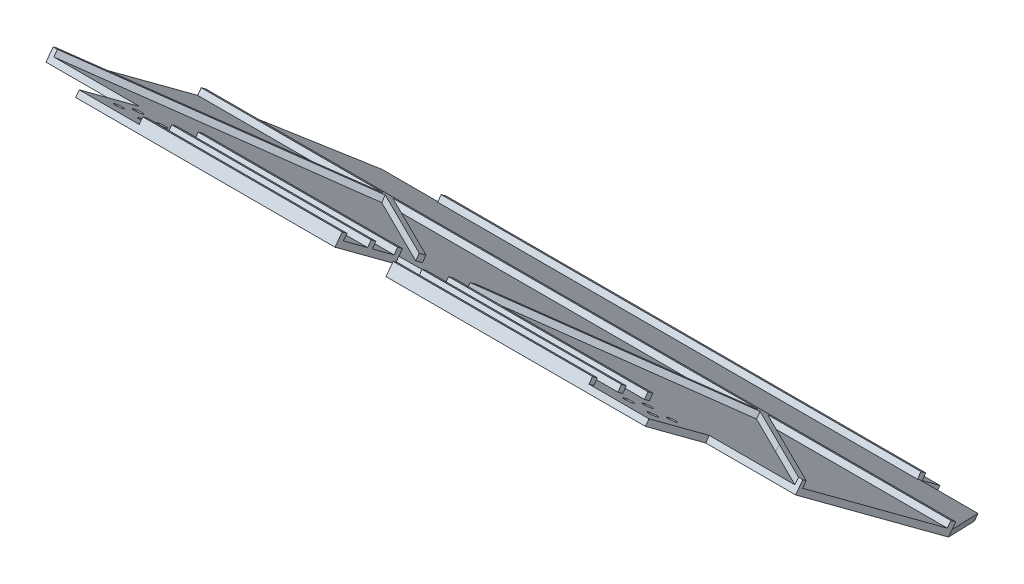
SolidWorks part; units mm, degrees
ref_plane "前视基准面" through (0, 0, 0) normal (0, 0, 1) x (1, 0, 0)
ref_plane "上视基准面" through (0, 0, 0) normal (0, 1, 0) x (1, 0, 0)
ref_plane "右视基准面" through (0, 0, 0) normal (1, 0, 0) x (0, 0, -1)
other "Configuration Table"
sketch "草图1" plane through (0, 0, 0) normal (0, 0, 1) x (1, 0, 0)
  line L11 (-17.5, -167.5) -> (167.5, -167.5)
  line L12 (-17.5, -167.5) -> (-17.5, 17.5)
  line L13 (-17.5, 17.5) -> (167.5, 17.5)
  line L14 (167.5, -167.5) -> (167.5, 17.5)
sketch "草图3" plane through (0, 0, 20) normal (0, 0, 1) x (1, 0, 0)
  line L7 (-32.4602, 32.2748) -> (182.5398, 32.2748)
  line L8 (-32.4602, 32.2748) -> (-32.4602, -182.7252)
  line L9 (-32.4602, -182.7252) -> (182.5398, -182.7252)
  line L10 (182.5398, 32.2748) -> (182.5398, -182.7252)
  point P12 (75.0398, -75.2252)
  dimension "D1" = 215
  dimension "D2" = 215
loft "放样1" add profiles "草图3", "草图1" connector at (-32.4602, 32.2748, 20) connector at (-17.5, 17.5, 0)
shell "抽壳2" thickness 3 removed face at (75.0398, -75.2252, 20)
sketch "草图4" plane through (0, 0, 3) normal (0, 0, 1) x (1, 0, 0)
  line L0 (75, 15.9864) -> (75, -182.7252)
  line L1 (166.0024, 15.9864) -> (-15.9976, 15.9864) construction
  line L2 (-32.4602, -182.7252) -> (182.5398, -182.7252) construction
  line L3 (-32.4602, -75.2252) -> (182.5398, -75.2252)
  line L4 (-32.4602, 32.2748) -> (-32.4602, -182.7252) construction
  line L5 (182.5398, -182.7252) -> (182.5398, 32.2748) construction
  circle A0 centre (66.25, -75.2252) radius 7 construction
  circle A1 centre (66.25, -75.2252) radius 4
  circle A2 centre (66.25, -68.2252) radius 1.5
  circle A3 centre (66.25, -82.2252) radius 1.5
  circle A4 centre (73.25, -75.2252) radius 1.5
  circle A5 centre (59.25, -75.2252) radius 1.5
  circle A6 centre (84.75, -75.2252) radius 1.5
  circle A7 centre (47.75, -75.2252) radius 1.5
  dimension "D1" = 8
  dimension "D2" = 14
  dimension "D3" = 3
  dimension "D4" = 3
  dimension "D5" = 3
  dimension "D6" = 3
  dimension "D7" = 3
  dimension "D8" = 3
  dimension "D9" = 37
  dimension "D10" = 18.5
extrude "切除-拉伸1" cut sketch "草图4" against normal blind 10 contours L3 A6 | L3 A6 | A3 | L3 A4 | L3 A4 | A2 | L3 A5 | L3 A5 | L3 A7 | L3 A7 region at (47.75, -74.5886, 3) region at (84.75, -74.5886, 3) region at (84.75, -75.8619, 3) region at (73.25, -74.5886, 3) region at (73.25, -75.8619, 3) region at (59.25, -74.5886, 3) region at (59.25, -75.8619, 3) region at (47.75, -75.8619, 3) region at (66.25, -68.2252, 3) region at (66.25, -82.2252, 3)
sketch "草图6" plane through (0, 0, 3) normal (0, 0, 1) x (1, 0, 0)
  line L2 (38.15, -62.5) -> (34.15, -62.5)
  line L5 (38.15, -75) -> (38.15, -62.5)
  line L6 (38.15, -75) -> (38.15, -87.5)
  line L7 (94.35, -75) -> (94.35, -62.5)
  line L8 (94.35, -75) -> (94.35, -87.5)
  line L9 (94.35, -62.5) -> (98.35, -62.5)
  line L11 (98.35, -87.5) -> (94.35, -87.5)
  line L12 (98.35, -87.5) -> (101.35, -87.5)
  line L13 (101.35, -87.5) -> (101.35, -84.5)
  line L14 (98.35, -62.5) -> (101.35, -62.5)
  line L15 (101.35, -62.5) -> (101.35, -65.5)
  line L16 (38.15, -87.5) -> (34.15, -87.5)
  line L17 (34.15, -62.5) -> (31.15, -62.5)
  line L18 (31.15, -62.5) -> (31.15, -65.5)
  line L19 (34.15, -87.5) -> (31.15, -87.5)
  line L20 (31.15, -87.5) -> (31.15, -84.5)
  line L21 (31.15, -65.5) -> (34.15, -65.5)
  line L22 (31.15, -84.5) -> (34.15, -84.5)
  line L23 (34.15, -84.5) -> (34.15, -65.5)
  line L24 (101.35, -65.5) -> (98.35, -65.5)
  line L25 (101.35, -84.5) -> (98.35, -84.5)
  line L26 (98.35, -84.5) -> (98.35, -65.5)
extrude "凸台-拉伸1" add sketch "草图6" against normal blind 40.5
sketch "草图7" plane through (98.35, 0, 0) normal (1, 0, 0) x (0, 0, -1)
  line L0 (0, -65.5) -> (0, -84.5)
  line L1 (0, -75) -> (16.5, -75)
  line L2 (16.5, -75) -> (33.5, -75)
  line L3 (33.5, -75) -> (37.5, -75)
  line L4 (37.5, -84.5) -> (37.5, -65.5) construction
  circle A0 centre (16.5, -75) radius 1.51
  circle A1 centre (33.5, -75) radius 1.51
extrude "切除-拉伸2" cut sketch "草图7" against normal blind 100 contours L2 A0 L1 | L1 A0 L2 | L3 A1 L2 | L2 A1 L3 region at (98.35, -74.3591, -16.5) region at (98.35, -74.3591, -33.5) region at (98.35, -75.6409, -33.5) region at (98.35, -75.6409, -16.5)
sketch "草图8" plane through (0, 0, 3) normal (0, 0, 1) x (1, 0, 0)
  circle A0 centre (66.25, -68.2252) radius 1.5
  circle A1 centre (59.25, -75.2252) radius 1.5
  circle A2 centre (47.75, -75.2252) radius 1.5
  circle A3 centre (73.25, -75.2252) radius 1.5
  circle A4 centre (84.75, -75.2252) radius 1.5
  circle A5 centre (66.25, -82.2252) radius 1.5
  circle M2 centre (84.75, -75.2252) radius 1.5
  circle M3 centre (59.25, -75.2252) radius 1.5
  circle M5 centre (73.25, -75.2252) radius 1.5
  circle M6 centre (66.25, -82.2252) radius 1.5
  circle M7 centre (47.75, -75.2252) radius 1.5
extrude "凸台-拉伸2" add sketch "草图8" against normal blind 3 contours M6 | M5 | M2 | M3 | M7 | A0 region at (59.25, -75.2252, 3) region at (47.75, -75.2252, 3) region at (73.25, -75.2252, 3) region at (84.75, -75.2252, 3) region at (66.25, -82.2252, 3)
sketch "草图9" plane through (0, 0, 0) normal (0, 0, -1) x (-1, 0, 0)
  line L3 (-73.5858, -76.4142) -> (0, -2.8284)
  line L4 (17.5, 17.5) -> (17.5, -167.5) construction
  line L5 (0, -2.8284) -> (0, 0)
  line L6 (-72.7486, -69.9202) -> (-2.8284, 0)
  line L7 (-167.5, 17.5) -> (17.5, 17.5) construction
  line L8 (-2.8284, 0) -> (0, 0)
  line L9 (-72.7486, -69.9202) -> (-150, -147.1716)
  line L10 (-167.5, -167.5) -> (-167.5, 17.5) construction
  line L11 (-150, -147.1716) -> (-150, -150)
  line L12 (-73.5858, -76.4142) -> (-147.1716, -150)
  line L14 (17.5, -167.5) -> (-167.5, -167.5) construction
  line L15 (-147.1716, -150) -> (-150, -150)
extrude "凸台-拉伸3" add sketch "草图9" along normal blind 4 contours L9 L11 L15 L12 L3 L5 L8 L6
sketch "草图10" plane through (0, 0, 0) normal (0, 0, -1) x (-1, 0, 0)
  line L3 (-106.6693, -40.5023) -> (-147.1716, 17.5)
  line L4 (-167.5, 17.5) -> (17.5, 17.5) construction
  line L5 (-147.1716, 17.5) -> (-167.5, 17.5)
  line L6 (-121.9738, -30.8546) -> (-167.5, 34.3423)
  line L7 (-167.5, -167.5) -> (-167.5, 17.5) construction
  line L8 (-167.5, 34.3423) -> (-167.5, 17.5)
  line L9 (-106.6693, -40.5023) -> (17.5, -218.322)
  line L10 (17.5, 17.5) -> (17.5, -167.5) construction
  line L11 (17.5, -218.322) -> (17.5, -167.5)
  line L12 (-121.9738, -30.8546) -> (-26.556, -167.5)
  line L13 (17.5, -167.5) -> (-167.5, -167.5) construction
  line L14 (-26.556, -167.5) -> (17.5, -167.5)
extrude "凸台-拉伸4" add sketch "草图10" along normal blind 4 contours L3 L5 L8 L6 L12 L14 L11 L9 rebuild error yes
sketch "草图11" plane through (0, 0, -4) normal (0, 0, -1) x (-1, 0, 0)
  line L1 (-94.35, -62.5) -> (-38.15, -62.5)
  line L2 (-94.35, -62.5) -> (-94.35, -87.5)
  line L3 (-94.35, -87.5) -> (-38.15, -87.5)
  line L4 (-38.15, -62.5) -> (-38.15, -87.5)
extrude "切除-拉伸3" cut sketch "草图11" against normal blind 4 contours L2 L1 L4 L3
sketch "草图12" plane through (0, 0, 20) normal (0, 0, 1) x (1, 0, 0)
  line L1 (182.5398, 32.2748) -> (185.5398, 32.2748)
  line L2 (182.5398, 32.2748) -> (182.5398, -182.7252)
  line L3 (182.5398, -182.7252) -> (185.5398, -182.7252)
  line L4 (185.5398, 32.2748) -> (185.5398, -182.7252)
extrude "凸台-拉伸5" add sketch "草图12" against normal blind 10 separate body
sketch "草图13" plane through (185.5398, 0, 0) normal (1, 0, 0) x (0, 0, -1)
  line L0 (-10, -182.7252) -> (-10, 32.2748) construction
  line L1 (-20, 32.2748) -> (-10, 32.2748)
  line L2 (-20, 32.2748) -> (-20, -182.7252)
  line L3 (-20, -182.7252) -> (-10, -182.7252)
  line L4 (-10, 32.2748) -> (-10, -182.7252)
extrude "切除-拉伸4" cut sketch "草图13" against normal blind 300
sketch "草图15" plane through (0, 0, -4) normal (0, 0, -1) x (-1, 0, 0)
  line L1 (-154.8521, -152.6743) -> (-38.15, -152.6743)
  line L2 (-154.8521, -152.6743) -> (-154.8521, -87.5)
  line L3 (-154.8521, -87.5) -> (-38.15, -87.5)
  line L4 (-38.15, -152.6743) -> (-38.15, -87.5)
  line L5 (-94.35, -62.5) -> (17.5, -62.5)
  line L6 (-94.35, -62.5) -> (-94.35, 17.5)
  line L7 (-94.35, 17.5) -> (17.5, 17.5)
  line L8 (17.5, -62.5) -> (17.5, 17.5)
extrude "切除-拉伸5" cut sketch "草图15" against normal blind 4 contours L6 L5 L8 L7 | L2 L1 L4 L3
sketch "草图16" plane through (0, 0, 0) normal (0, 0, -1) x (-1, 0, 0)
  line L3 (-123.7693, -120.9409) -> (-167.5, -164.6716)
  line L4 (-134.8709, -12.3007) -> (-164.6716, 17.5)
  line L5 (-167.5, 17.5) -> (17.5, 17.5) construction
  line L6 (-164.6716, 17.5) -> (-167.5, 17.5)
  line L7 (-140.0326, -12.7959) -> (-167.5, 14.6716)
  line L8 (-167.5, -167.5) -> (-167.5, 17.5) construction
  line L9 (-167.5, 14.6716) -> (-167.5, 17.5)
  line L10 (-140.0326, -12.7959) -> (14.6716, -167.5)
  line L11 (17.5, -167.5) -> (-167.5, -167.5) construction
  line L12 (14.6716, -167.5) -> (17.5, -167.5)
  line L14 (-134.8709, -12.3007) -> (17.5, -164.6716)
  line L15 (17.5, 17.5) -> (17.5, -167.5) construction
  line L16 (17.5, -164.6716) -> (17.5, -167.5)
  line L17 (-167.5, -164.6716) -> (-167.5, -167.5)
  line L18 (-116.3532, -119.1816) -> (-164.6716, -167.5)
  line L19 (-164.6716, -167.5) -> (-167.5, -167.5)
  line L20 (-116.3532, -119.1816) -> (17.5, 14.6716)
  line L21 (17.5, 14.6716) -> (17.5, 17.5)
  line L22 (-123.7693, -120.9409) -> (14.6716, 17.5)
  line L23 (14.6716, 17.5) -> (17.5, 17.5)
extrude "凸台-拉伸6" add sketch "草图16" along normal blind 4 contours L10 L22 L14 L4 L7 | L20 L10 L14 | L3 L17 L19 L18 L20 L21 L23 L22 region at (121.6045, -28.3955, 0) region at (28.3955, -121.6045, 0)
sketch "草图17" plane through (0, 0, 0) normal (0, 0, -1) x (-1, 0, 0)
  line L1 (-94.35, -62.5) -> (-38.15, -62.5)
  line L2 (-94.35, -62.5) -> (-94.35, -87.5)
  line L3 (-94.35, -87.5) -> (-38.15, -87.5)
  line L4 (-38.15, -62.5) -> (-38.15, -87.5)
extrude "切除-拉伸6" cut sketch "草图17" along normal blind 4 contours L2 L1 L4 L3
sketch "草图18" plane through (0, 0, 0) normal (0, 0, -1) x (-1, 0, 0)
  line L3 (-75, -119.25) -> (-33.5784, -119.25)
  line L7 (-65.3284, -87.5) -> (14.6716, -167.5) construction
  line L8 (-33.5784, -119.25) -> (-31.5784, -121.25)
  line L9 (-65.3284, -87.5) -> (14.6716, -167.5) construction
  line L10 (-75, -123.25) -> (-29.5784, -123.25)
  line L11 (-29.5784, -123.25) -> (-31.5784, -121.25)
  line L12 (-75, -119.25) -> (-116.4216, -119.25)
  line L13 (-164.6716, -167.5) -> (-84.6716, -87.5) construction
  line L14 (-75, -123.25) -> (-120.4216, -123.25)
  line L15 (-120.4216, -123.25) -> (-116.4216, -119.25)
  line L18 (-119.25, -75) -> (-119.25, -116.4216)
  line L19 (-90.3284, -87.5) -> (-167.5, -164.6716) construction
  line L20 (-119.25, -116.4216) -> (-121.25, -118.4216)
  line L21 (-123.25, -75) -> (-123.25, -120.4216)
  line L22 (-123.25, -120.4216) -> (-121.25, -118.4216)
  line L23 (-119.25, -75) -> (-119.25, -33.5784)
  line L24 (-167.5, 14.6716) -> (-90.3284, -62.5) construction
  line L25 (-123.25, -75) -> (-123.25, -29.5784)
  line L26 (-167.5, 14.6716) -> (-90.3284, -62.5) construction
  line L27 (-123.25, -29.5784) -> (-119.25, -33.5784)
  line L30 (-75, -30.75) -> (-116.4216, -30.75)
  line L31 (-164.6716, 17.5) -> (-84.6716, -62.5) construction
  line L32 (-75, -26.75) -> (-120.4216, -26.75)
  line L33 (-164.6716, 17.5) -> (-84.6716, -62.5) construction
  line L34 (-120.4216, -26.75) -> (-116.4216, -30.75)
  line L35 (-75, -30.75) -> (-33.5784, -30.75)
  line L36 (14.6716, 17.5) -> (-65.3284, -62.5) construction
  line L37 (-75, -26.75) -> (-29.5784, -26.75)
  line L38 (-65.3284, -62.5) -> (14.6716, 17.5) construction
  line L39 (-29.5784, -26.75) -> (-33.5784, -30.75)
  line L40 (-30.75, -33.5784) -> (-26.75, -29.5784)
  line L42 (-26.75, -75) -> (-26.75, -29.5784)
  line L43 (-59.6716, -62.5) -> (17.5, 14.6716) construction
  line L44 (-30.75, -75) -> (-30.75, -33.5784)
  line L45 (-30.75, -75) -> (-30.75, -116.4216)
  line L46 (-59.6716, -87.5) -> (17.5, -164.6716) construction
  line L47 (-26.75, -75) -> (-26.75, -120.4216)
  line L48 (-30.75, -116.4216) -> (-26.75, -120.4216)
extrude "凸台-拉伸7" add sketch "草图18" along normal blind 4
sketch "草图20" plane through (0, 0, 0) normal (0, 0, -1) x (-1, 0, 0)
  line L0 (-94.35, -62.5) -> (-94.35, -87.5)
  line L1 (-94.35, -87.5) -> (-38.15, -87.5)
  line L2 (-38.15, -87.5) -> (-38.15, -62.5)
  line L3 (-38.15, -62.5) -> (-94.35, -62.5)
  line L4 (-66.25, -75) -> (-66.25, -82)
  line L5 (-66.25, -75) -> (-47.75, -75)
  line L6 (-66.25, -75) -> (-84.75, -75)
  line L7 (-66.25, -75) -> (-66.25, -68)
  circle A0 centre (-84.75, -75) radius 1.5
  circle A1 centre (-47.75, -75) radius 1.5
  circle A2 centre (-66.25, -68) radius 1.5
  circle A3 centre (-66.25, -82) radius 1.5
extrude "切除-拉伸7" cut sketch "草图20" against normal blind 10 contours A2 | A0 | A3 | A1 region at (65.2193, -80.9693, 0) region at (47.75, -73.5424, 0) region at (86.2076, -75, 0) region at (67.2807, -66.9693, 0)
sketch "草图21" plane through (0, 0, -37.5) normal (0, 0, -1) x (-1, 0, 0)
  line L1 (-167.5, 17.5) -> (17.5, 17.5)
  line L2 (-167.5, 17.5) -> (-167.5, -167.5)
  line L3 (-167.5, -167.5) -> (17.5, -167.5)
  line L4 (17.5, 17.5) -> (17.5, -167.5)
extrude "切除-拉伸8" cut sketch "草图21" against normal blind 37.5
sketch "草图22" plane through (0, 0, 0) normal (0, 0, -1) x (-1, 0, 0)
  line L1 (17.5, 17.5) -> (-167.5, 17.5)
  line L2 (17.5, 17.5) -> (17.5, -167.5)
  line L3 (17.5, -167.5) -> (-167.5, -167.5)
  line L4 (-167.5, 17.5) -> (-167.5, -167.5)
  circle A0 centre (-66.25, -68) radius 1.5
  circle A1 centre (-66.25, -82) radius 1.5
  circle A2 centre (-84.75, -75) radius 1.5
  circle A3 centre (-47.75, -75) radius 1.5
extrude "凸台-拉伸8" add sketch "草图22" along normal blind 1 contours L2 L1 L4 L3 | A3 | A0 | A2 | A1
sketch "草图24" plane through (0, 0, 3) normal (0, 0, 1) x (1, 0, 0)
  circle A0 centre (66.25, -68) radius 3
  circle A1 centre (66.25, -82) radius 3
  circle A2 centre (47.75, -75) radius 3
  circle A3 centre (84.75, -75) radius 3
  circle M4 centre (66.25, -68) radius 1.5
  circle M5 centre (84.75, -75) radius 1.5
  circle M6 centre (66.25, -82) radius 1.5
extrude "切除-拉伸9" cut sketch "草图24" against normal blind 2 contours A0 M4 | A1 M6 | A3 M5 | A2 region at (63.3349, -68, 3) region at (63.3349, -82, 3) region at (81.8349, -75, 3)
sketch "草图25" plane through (0, 0, -1) normal (0, 0, -1) x (-1, 0, 0)
  line L0 (-167.5, 17.5) -> (17.5, -167.5)
  line L1 (-75, -75) -> (-75, -68)
  line L2 (-75, -75) -> (-75, -82)
  line L4 (-75, -75) -> (-56.5, -75)
  line L5 (-75, -75) -> (-93.5, -75)
  circle A0 centre (-75, -68) radius 1.51
  circle A1 centre (-75, -82) radius 1.51
  circle A2 centre (-93.5, -75) radius 1.51
  circle A3 centre (-56.5, -75) radius 1.51
extrude "切除-拉伸10" cut sketch "草图25" against normal blind 10 contours A2 | A0 | A1 | A3 region at (76.0375, -66.9625, -1) region at (73.9625, -80.9625, -1) region at (56.5, -73.5327, -1) region at (94.9673, -75, -1)
sketch "草图26" plane through (0, 0, -1) normal (0, 0, -1) x (-1, 0, 0)
  circle A0 centre (-84.75, -75) radius 1.5
  circle A1 centre (-66.25, -68) radius 1.5
  circle A2 centre (-66.25, -82) radius 1.5
  circle A3 centre (-47.75, -75) radius 1.5
extrude "凸台-拉伸9" add sketch "草图26" against normal blind 4 contours A0 | A1 | A2 | A3
sketch "草图28" plane through (0, 0, 3) normal (0, 0, 1) x (1, 0, 0)
  circle A0 centre (84.75, -75) radius 3
  circle A1 centre (66.25, -68) radius 3
  circle A2 centre (47.75, -75) radius 3
  circle A3 centre (66.25, -82) radius 3
extrude "凸台-拉伸10" add sketch "草图28" against normal blind 4
sketch "草图29" plane through (0, 0, 3) normal (0, 0, 1) x (1, 0, 0)
  circle A0 centre (75, -68) radius 3
  circle A1 centre (75, -82) radius 3
  circle A2 centre (93.5, -75) radius 3
  circle A3 centre (56.5, -75) radius 3
extrude "切除-拉伸11" cut sketch "草图29" against normal blind 2
sketch "草图30" plane through (0, 0, 10) normal (0, 0, 1) x (1, 0, 0)
  line L0 (-24.9801, 24.8874) -> (175.0199, -175.1126)
  line L1 (-124.9801, 124.8874) -> (-104.9801, 124.8874)
  line L2 (-104.9801, 124.8874) -> (-104.9801, 104.8874)
  line L5 (-124.9801, -75.1126) -> (-124.9801, 124.8874)
  line L6 (-124.9801, 124.8874) -> (75.0199, 124.8874)
  line L7 (275.0199, -75.1126) -> (275.0199, 124.8874)
  line L8 (275.0199, 124.8874) -> (75.0199, 124.8874)
  line L9 (-124.9801, -75.1126) -> (-124.9801, -275.1126)
  line L10 (-124.9801, -275.1126) -> (75.0199, -275.1126)
  line L12 (275.0199, -275.1126) -> (75.0199, -275.1126)
  line L13 (275.0199, -275.1126) -> (275.0199, -255.1126)
  line L14 (275.0199, -255.1126) -> (255.0199, -255.1126)
  line L16 (-104.9801, 104.8874) -> (255.0199, 104.8874)
  line L17 (-104.9801, 104.8874) -> (-104.9801, -255.1126)
  line L18 (-104.9801, -255.1126) -> (255.0199, -255.1126)
  line L19 (255.0199, 104.8874) -> (255.0199, -255.1126)
  line L20 (255.0199, 104.8874) -> (275.0199, 104.8874)
  line L21 (255.0199, 104.8874) -> (255.0199, 124.8874)
  line L22 (255.0199, 124.8874) -> (275.0199, 124.8874)
  line L23 (275.0199, 104.8874) -> (275.0199, 124.8874)
  line L24 (-104.9801, 104.8874) -> (-124.9801, 104.8874)
  line L25 (-104.9801, 104.8874) -> (-104.9801, 124.8874)
  line L26 (-104.9801, 124.8874) -> (-124.9801, 124.8874)
  line L27 (-124.9801, 104.8874) -> (-124.9801, 124.8874)
  line L28 (-104.9801, -255.1126) -> (-124.9801, -255.1126)
  line L29 (-104.9801, -255.1126) -> (-104.9801, -275.1126)
  line L30 (-104.9801, -275.1126) -> (-124.9801, -275.1126)
  line L31 (-124.9801, -255.1126) -> (-124.9801, -275.1126)
  line L32 (255.0199, -255.1126) -> (275.0199, -255.1126)
  line L33 (255.0199, -255.1126) -> (255.0199, -275.1126)
  line L34 (255.0199, -275.1126) -> (275.0199, -275.1126)
  line L35 (275.0199, -255.1126) -> (275.0199, -275.1126)
extrude "凸台-拉伸11" add sketch "草图30" along normal blind 300 separate body contours L24 L2 L1 L5 | L21 L20 L7 L8 | L29 L28 L9 L10 | L14 L33 L12 L13 region at (-114.9801, 114.8874, 10) region at (265.0199, 114.8874, 10) region at (-114.9801, -265.1126, 10) region at (265.0199, -265.1126, 10)
sketch "草图31" plane through (0, 0, 10) normal (0, 0, -1) x (-1, 0, 0)
  line L0 (-275.0199, -275.1126) -> (-255.0199, -275.1126) construction
  line L1 (-275.0199, 124.8874) -> (-255.0199, 124.8874)
  line L2 (-275.0199, 124.8874) -> (-275.0199, 104.8874)
  line L3 (-275.0199, 104.8874) -> (-255.0199, 104.8874)
  line L4 (-255.0199, 124.8874) -> (-255.0199, 104.8874)
  line L5 (104.9801, 124.8874) -> (124.9801, 124.8874)
  line L6 (104.9801, 124.8874) -> (104.9801, 104.8874)
  line L7 (104.9801, 104.8874) -> (124.9801, 104.8874)
  line L8 (124.9801, 124.8874) -> (124.9801, 104.8874)
  line L9 (104.9801, -255.1126) -> (124.9801, -255.1126)
  line L10 (104.9801, -255.1126) -> (104.9801, -275.1126)
  line L11 (104.9801, -275.1126) -> (124.9801, -275.1126)
  line L12 (124.9801, -255.1126) -> (124.9801, -275.1126)
  line L13 (-275.0199, -255.1126) -> (-255.0199, -255.1126)
  line L14 (-275.0199, -255.1126) -> (-275.0199, -275.1126)
  line L15 (-275.0199, -275.1126) -> (-255.0199, -275.1126)
  line L16 (-255.0199, -255.1126) -> (-255.0199, -275.1126)
extrude "凸台-拉伸12" add sketch "草图31" along normal blind 300
sketch "草图32" plane through (0, 11.3215, -8.3636) normal (0, 0.8043, -0.5942) x (1, 0, 0)
  line L0 (-24.9801, -22.831) -> (-19.37, -13.5065)
  line L1 (-24.9801, -22.831) -> (-104.9801, -155.7995)
  line L2 (-104.9801, -323.5478) -> (-104.9801, 159.0484) construction
  line L3 (-104.9801, -155.7995) -> (255.0199, -155.7995)
  line L4 (255.0199, -323.5478) -> (255.0199, 159.0484) construction
  line L5 (255.0199, -155.7995) -> (175.0199, -22.831)
  line L6 (169.38, -13.5065) -> (175.0199, -22.831)
  line L9 (-19.37, -13.5065) -> (169.38, -13.5065)
extrude "凸台-拉伸13" add sketch "草图32" along normal blind 2
sketch "草图33" plane through (0, 12.9301, -9.552) normal (0, 0.8043, -0.5942) x (1, 0, 0)
  line L0 (-24.9801, -22.831) -> (175.0199, -22.831)
  line L2 (170.16, -20.831) -> (173.8102, -20.831)
  line L3 (175.0199, -22.831) -> (169.38, -13.5065) construction
  line L4 (173.8102, -20.831) -> (175.0199, -22.831)
  line L5 (170.16, -20.831) -> (-23.7768, -20.831)
  line L6 (-19.37, -13.5065) -> (-104.9801, -155.7995) construction
  line L7 (-23.7768, -20.831) -> (-24.9801, -22.831)
extrude "凸台-拉伸14" add sketch "草图33" along normal blind 2
sketch "草图34" plane through (0, 92.574, 125.3137) normal (0, 0.5942, 0.8043) x (1, 0, 0)
  line L1 (-104.9801, 14.0757) -> (255.0199, 14.0757)
  line L2 (-104.9801, 14.0757) -> (-104.9801, 16.0757)
  line L3 (-104.9801, 16.0757) -> (255.0199, 16.0757)
  line L4 (255.0199, 14.0757) -> (255.0199, 16.0757)
extrude "凸台-拉伸15" add sketch "草图34" along normal blind 40
sketch "草图35" plane through (255.0199, 0, 0) normal (1, 0, 0) x (0, 0, -1)
  line L0 (-149.1232, 127.6629) -> (-145.366, 124.8874)
  line L1 (-145.366, 124.8874) -> (-142.0001, 124.8874)
  line L2 (-142.0001, 124.8874) -> (-147.9348, 129.2716)
  line L3 (-147.9348, 129.2716) -> (-149.1232, 127.6629)
extrude "切除-拉伸12" cut sketch "草图35" against normal blind 400
sketch "草图36" plane through (0, 11.3215, -8.3636) normal (0, -0.8043, 0.5942) x (1, 0, 0)
  line L1 (-104.9801, 155.7995) -> (255.0199, 155.7995)
  line L2 (-104.9801, 155.7995) -> (-104.9801, 191.1283)
  line L3 (-104.9801, 191.1283) -> (255.0199, 191.1283)
  line L4 (255.0199, 155.7995) -> (255.0199, 191.1283)
extrude "切除-拉伸13" cut sketch "草图36" against normal blind 1
sketch "草图38" plane through (0, 12.9301, -9.552) normal (0, 0.8043, -0.5942) x (1, 0, 0)
  line L0 (-104.9801, -155.7995) -> (-104.9801, -188.4209)
  line L1 (-104.9801, -172.1102) -> (255.0199, -172.1102)
  line L2 (255.0199, -188.4209) -> (255.0199, -155.7995) construction
  line L3 (255.0199, -172.1102) -> (255.0199, -155.7995)
  line L4 (255.0199, -172.1102) -> (255.0199, -188.4209)
  line L5 (255.0199, -188.4209) -> (175.0199, -188.4209)
  line L6 (-104.9801, -188.4209) -> (255.0199, -188.4209) construction
  line L7 (-104.9801, -188.4209) -> (-24.9801, -188.4209)
  line L8 (255.0199, -189.7746) -> (-104.9801, -189.7746) construction
  line L9 (175.0199, -188.4209) -> (255.0199, -188.4209)
  line L10 (175.0199, -188.4209) -> (175.0199, -155.7995)
  line L11 (175.0199, -155.7995) -> (255.0199, -155.7995)
  line L12 (255.0199, -188.4209) -> (255.0199, -155.7995)
  line L13 (175.0199, -188.4209) -> (255.0199, -188.4209)
  line L14 (175.0199, -188.4209) -> (175.0199, -189.7746)
  line L15 (175.0199, -189.7746) -> (255.0199, -189.7746)
  line L16 (255.0199, -188.4209) -> (255.0199, -189.7746)
  line L17 (-24.9801, -188.4209) -> (-104.9801, -188.4209)
  line L18 (-24.9801, -188.4209) -> (-24.9801, -155.7995)
  line L19 (-24.9801, -155.7995) -> (-104.9801, -155.7995)
  line L20 (-104.9801, -188.4209) -> (-104.9801, -155.7995)
  line L21 (-24.9801, -188.4209) -> (-104.9801, -188.4209)
  line L22 (-24.9801, -188.4209) -> (-24.9801, -189.7746)
  line L23 (-24.9801, -189.7746) -> (-104.9801, -189.7746)
  line L24 (-104.9801, -188.4209) -> (-104.9801, -189.7746)
  line M3 (-104.9801, -155.7995) -> (-104.9801, -188.4209)
  line M4 (-104.9801, -188.4209) -> (255.0199, -188.4209)
  line M5 (255.0199, -188.4209) -> (255.0199, -155.7995)
extrude "切除-拉伸16" cut sketch "草图38" against normal blind 3 contours L10 L1 M4 M5 | L11 L10 L1 M5 | L16 L14 L15 M4 | L24 L23 L22 M4 | L18 L1 L0 M4 | L18 L19 L1 M3 region at (-64.9801, 110.3499, 122.3213) region at (-64.9801, 120.0416, 135.4405) region at (-64.9801, 125.2895, 142.5445) region at (215.0199, 110.3499, 122.3213) region at (215.0199, 120.0416, 135.4405) region at (215.0199, 125.2895, 142.5445)
sketch "草图40" plane through (0, 11.3215, -8.3636) normal (0, -0.8043, 0.5942) x (1, 0, 0)
  line L0 (-24.9801, 172.787) -> (-24.9801, 152.787)
  line L1 (-24.9801, 155.7995) -> (-24.9801, 189.7746) construction
  line L2 (-24.9801, 152.787) -> (0.0199, 152.787)
  line L4 (-24.9801, 152.787) -> (-24.9801, 127.787)
  line L7 (175.0199, 189.7746) -> (175.0199, 155.7995) construction
  line L8 (175.0199, 172.787) -> (175.0199, 152.787)
  line L9 (175.0199, 152.787) -> (150.0199, 152.787)
  line L12 (175.0199, 127.787) -> (175.0199, 152.787)
  line L14 (175.0199, 127.787) -> (255.0199, 127.787)
  line L15 (175.0199, 127.787) -> (175.0199, 155.7995)
  line L16 (175.0199, 155.7995) -> (255.0199, 155.7995)
  line L17 (255.0199, 127.787) -> (255.0199, 155.7995)
  line L18 (-24.9801, 127.787) -> (-104.9801, 127.787)
  line L19 (-24.9801, 127.787) -> (-24.9801, 155.7995)
  line L20 (-24.9801, 155.7995) -> (-104.9801, 155.7995)
  line L21 (-104.9801, 127.787) -> (-104.9801, 155.7995)
  line L22 (-24.9801, 152.787) -> (175.0199, 152.787)
  line L23 (-24.9801, 152.787) -> (-24.9801, 189.7746)
  line L24 (-24.9801, 189.7746) -> (175.0199, 189.7746)
  line L25 (175.0199, 152.787) -> (175.0199, 189.7746)
  circle A0 centre (156.0199, 143.787) radius 1.5
  circle A1 centre (164.0199, 143.787) radius 1.5
  circle A2 centre (164.0199, 135.787) radius 1.5
  circle A3 centre (156.0199, 135.787) radius 1.5
  circle A4 centre (-13.9801, 143.787) radius 1.5
  circle A5 centre (-5.9801, 143.787) radius 1.5
  circle A6 centre (-13.9801, 135.787) radius 1.5
  circle A7 centre (-5.9801, 135.787) radius 1.5
  line M33 (175.0199, 22.831) -> (255.0199, 155.7995)
  line M34 (255.0199, 155.7995) -> (-104.9801, 155.7995)
  line M35 (-104.9801, 155.7995) -> (-24.9801, 22.831)
extrude "切除-拉伸17" cut sketch "草图40" against normal blind 3 contours L18 L4 L0 M34 M35 | L2 L22 L9 L8 L0 M34 | L8 L25 L24 L23 L0 M34 | L21 L18 M35 | A5 | A4 | A6 | A7 | L12 L14 L8 M33 M34 | A1 | A0 | A3 | A2 | L14 L17 M33 region at (75.0199, 113.9893, 130.6137) region at (75.0199, 103.0005, 115.7386) region at (-60.9321, 95.8998, 106.1267) region at (-99.3623, 92.7991, 101.9293) region at (210.9718, 95.8998, 106.1267) region at (249.402, 92.7991, 101.9293) region at (156.0199, 96.7578, 107.2882) region at (164.0199, 96.7578, 107.2882) region at (164.0199, 92.0043, 100.8536) region at (156.0199, 92.0043, 100.8536) region at (-13.9801, 96.7578, 107.2882) region at (-5.9801, 96.7578, 107.2882) region at (-13.9801, 92.0043, 100.8536) region at (-5.9801, 92.0043, 100.8536)
sketch "草图41" plane through (0, 11.3215, -8.3636) normal (0, -0.8043, 0.5942) x (-1, 0, 0)
  line L0 (24.9801, -152.787) -> (-175.0199, -152.787)
  line L1 (24.9801, -22.831) -> (-175.0199, -22.831)
  line L2 (-75.0199, -22.831) -> (-75.0199, -152.787)
  line L3 (-75.0199, -87.809) -> (-200.0199, -87.809)
  line L4 (-200.0199, -87.809) -> (-200.0199, -127.787)
  line L5 (-175.0199, -127.787) -> (-238.1663, -127.787) construction
  line L6 (-200.0199, -127.787) -> (-238.1663, -127.787)
  line L7 (-200.0199, -87.809) -> (-200.0199, -64.3837)
  line L8 (-238.1663, -127.787) -> (-175.0199, -22.831) construction
  line L9 (-200.0199, -64.3837) -> (-238.1663, -127.787)
  line L10 (-75.0199, -87.809) -> (49.9801, -87.809)
  line L11 (49.9801, -87.809) -> (49.9801, -127.787)
  line L12 (24.9801, -127.787) -> (88.1265, -127.787) construction
  line L13 (49.9801, -127.787) -> (88.1265, -127.787)
  line L14 (49.9801, -87.809) -> (49.9801, -64.3837)
  line L15 (24.9801, -22.831) -> (88.1265, -127.787) construction
  line L16 (49.9801, -64.3837) -> (88.1265, -127.787)
  line M11 (24.9801, -127.787) -> (88.1265, -127.787)
  line M12 (88.1265, -127.787) -> (24.9801, -22.831)
  line M14 (-175.0199, -22.831) -> (-238.1663, -127.787)
  line M15 (-238.1663, -127.787) -> (-175.0199, -127.787)
extrude "切除-拉伸18" cut sketch "草图41" against normal blind 3 contours L14 L11 M11 M12 | L4 L7 M14 M15 region at (-62.6956, 74.693, 77.4199) region at (212.7354, 74.693, 77.4199)
sketch "草图42" plane through (0, 0, -290) normal (0, 0, -1) x (-1, 0, 0)
  line L0 (104.9801, 104.8874) -> (124.9801, 104.8874) construction
  line L1 (-275.0199, 124.8874) -> (-255.0199, 124.8874)
  line L2 (-275.0199, 124.8874) -> (-275.0199, 104.8874)
  line L3 (-275.0199, 104.8874) -> (-255.0199, 104.8874)
  line L4 (-255.0199, 124.8874) -> (-255.0199, 104.8874)
  line L5 (-275.0199, -255.1126) -> (-255.0199, -255.1126)
  line L6 (-275.0199, -255.1126) -> (-275.0199, -275.1126)
  line L7 (-275.0199, -275.1126) -> (-255.0199, -275.1126)
  line L8 (-255.0199, -255.1126) -> (-255.0199, -275.1126)
  line L9 (104.9801, -255.1126) -> (124.9801, -255.1126)
  line L10 (104.9801, -255.1126) -> (104.9801, -275.1126)
  line L11 (104.9801, -275.1126) -> (124.9801, -275.1126)
  line L12 (124.9801, -255.1126) -> (124.9801, -275.1126)
  line L13 (104.9801, 124.8874) -> (124.9801, 124.8874)
  line L14 (104.9801, 124.8874) -> (104.9801, 104.8874)
  line L15 (104.9801, 104.8874) -> (124.9801, 104.8874)
  line L16 (124.9801, 124.8874) -> (124.9801, 104.8874)
  line L17 (-175.0199, 24.8874) -> (-175.0199, -175.1126) construction
  line L18 (-175.0199, 19.3468) -> (24.9801, 19.3468)
  line L19 (-175.0199, 19.3468) -> (-175.0199, -175.1126)
  line L20 (-175.0199, -175.1126) -> (24.9801, -175.1126)
  line L21 (24.9801, 19.3468) -> (24.9801, -175.1126)
extrude "切除-拉伸19" cut sketch "草图42" against normal blind 1000
sketch "草图43" plane through (0, 11.3215, -8.3636) normal (0, -0.8043, 0.5942) x (1, 0, 0)
  line L1 (-24.9801, 22.831) -> (175.0199, 22.831)
  line L2 (-24.9801, 22.831) -> (-24.9801, 12.8195)
  line L3 (-24.9801, 12.8195) -> (175.0199, 12.8195)
  line L4 (175.0199, 22.831) -> (175.0199, 12.8195)
extrude "切除-拉伸20" cut sketch "草图43" along normal blind 1000
sketch "草图44" plane through (0, 11.3215, -8.3636) normal (0, -0.8043, 0.5942) x (1, 0, 0)
  line L0 (-24.9801, 152.787) -> (175.0199, 152.787) construction
  line L1 (-24.9801, 127.787) -> (-19.9801, 127.787)
  line L2 (-24.9801, 127.787) -> (-24.9801, 152.787)
  line L3 (-24.9801, 152.787) -> (-19.9801, 152.787)
  line L4 (-19.9801, 127.787) -> (-19.9801, 152.787)
  line L6 (175.0199, 127.787) -> (170.0199, 127.787)
  line L7 (175.0199, 127.787) -> (175.0199, 152.787)
  line L8 (175.0199, 152.787) -> (170.0199, 152.787)
  line L9 (170.0199, 127.787) -> (170.0199, 152.787)
extrude "切除-拉伸21" cut sketch "草图44" against normal blind 5 contours L2 L1 L4 L3 | L7 L6 L9 L8
sketch "草图46" plane through (0, 12.9301, -9.552) normal (0, 0.8043, -0.5942) x (1, 0, 0)
  line L0 (170.0199, -127.787) -> (170.0199, -152.787) construction
  line L1 (-19.9801, -152.787) -> (170.0199, -152.787)
  line L2 (-19.9801, -152.787) -> (-19.9801, -150.787)
  line L3 (-19.9801, -150.787) -> (170.0199, -150.787)
  line L4 (170.0199, -152.787) -> (170.0199, -150.787)
  line L6 (-19.9801, -127.787) -> (170.0199, -127.787)
  line L7 (-19.9801, -127.787) -> (-19.9801, -129.787)
  line L8 (-19.9801, -129.787) -> (170.0199, -129.787)
  line L9 (170.0199, -127.787) -> (170.0199, -129.787)
  line L11 (-19.9801, -127.787) -> (-19.9801, -152.787) construction
  line L12 (-19.9801, -139.787) -> (-19.9801, -140.787)
  line L14 (-19.9801, -140.787) -> (170.0199, -140.787)
  line L15 (-19.9801, -140.787) -> (-19.9801, -138.787)
  line L16 (-19.9801, -138.787) -> (170.0199, -138.787)
  line L17 (170.0199, -140.787) -> (170.0199, -138.787)
  line M17 (-19.9801, -127.787) -> (-19.9801, -152.787)
  line M18 (-19.9801, -152.787) -> (170.0199, -152.787)
  line M19 (170.0199, -152.787) -> (170.0199, -127.787)
extrude "凸台-拉伸16" add sketch "草图46" along normal blind 2 contours L8 L6 M17 M19 | L16 L14 M17 M19 | L3 M17 M18 M19 region at (75.0199, 103.12, 112.5344) region at (75.0199, 95.9897, 102.8825) region at (75.0199, 89.4537, 94.0349)
sketch "草图47" plane through (0, 12.9301, -9.552) normal (0, 0.8043, -0.5942) x (1, 0, 0)
  line L0 (-19.9801, -152.787) -> (170.0199, -152.787) construction
  line L1 (-19.9801, -127.787) -> (0.0199, -127.787)
  line L2 (-19.9801, -127.787) -> (-19.9801, -152.787)
  line L3 (-19.9801, -152.787) -> (0.0199, -152.787)
  line L4 (0.0199, -127.787) -> (0.0199, -152.787)
  line L6 (170.0199, -127.787) -> (150.0199, -127.787)
  line L7 (170.0199, -127.787) -> (170.0199, -152.787)
  line L8 (170.0199, -152.787) -> (150.0199, -152.787)
  line L9 (150.0199, -127.787) -> (150.0199, -152.787)
extrude "切除-拉伸22" cut sketch "草图47" along normal blind 2
sketch "草图48" plane through (0, 12.9301, -9.552) normal (0, 0.8043, -0.5942) x (1, 0, 0)
  line L0 (-49.9801, -64.3837) -> (200.0199, -64.3837)
  line L1 (200.0199, -64.3837) -> (200.0199, -127.787) construction
  line L2 (-49.9801, -64.3837) -> (200.0199, -64.3837)
  line L3 (-49.9801, -64.3837) -> (-49.9801, -66.3837)
  line L4 (-49.9801, -66.3837) -> (200.0199, -66.3837)
  line L5 (200.0199, -64.3837) -> (200.0199, -66.3837)
  line M19 (200.0199, -127.787) -> (200.0199, -64.3837)
  line M23 (-49.9801, -64.3837) -> (-49.9801, -127.787)
extrude "凸台-拉伸17" add sketch "草图48" along normal blind 2 contours L4 L0 M23 M19 region at (75.0199, 51.7802, 43.0379)
sketch "草图49" plane through (0, 12.9301, -9.552) normal (0, 0.8043, -0.5942) x (1, 0, 0)
  line L3 (-18.0293, -97.7987) -> (13.9468, -66.3837)
  line L4 (-18.0293, -97.7987) -> (-48.5532, -127.787)
  line L5 (0.0199, -127.787) -> (150.0199, -127.787) construction
  line L6 (44.4707, -96.372) -> (76.4467, -127.787)
  line L8 (136.0931, -66.3837) -> (138.9468, -66.3837)
  line L9 (106.977, -97.7924) -> (76.4467, -127.787)
  line L10 (-19.9801, -127.787) -> (-49.9801, -127.787) construction
  line L11 (-48.5532, -127.787) -> (-49.9801, -127.787)
  line L12 (-19.4309, -96.372) -> (-49.9801, -126.3852)
  line L13 (-49.9801, -127.787) -> (-49.9801, -66.3837) construction
  line L14 (-49.9801, -126.3852) -> (-49.9801, -127.787)
  line L15 (-49.9801, -66.3837) -> (200.0199, -66.3837) construction
  line L16 (-19.4309, -96.372) -> (11.093, -66.3837)
  line L17 (-49.9801, -66.3837) -> (200.0199, -66.3837) construction
  line L20 (43.0691, -97.7987) -> (11.093, -66.3837)
  line L21 (44.4707, -96.372) -> (13.9468, -66.3837)
  line L22 (11.093, -66.3837) -> (12.5199, -66.3837)
  line L23 (12.5199, -66.3837) -> (13.9468, -66.3837)
  line L25 (43.0691, -97.7987) -> (73.593, -127.787)
  line L26 (105.5628, -96.3782) -> (73.593, -127.787)
  line L27 (73.593, -127.787) -> (76.4467, -127.787)
  line L33 (105.5628, -96.3782) -> (136.0931, -66.3837)
  line L36 (138.9468, -66.3837) -> (106.977, -97.7924)
  line L40 (169.4707, -96.372) -> (200.0199, -126.3852)
  line L42 (200.0199, -66.3837) -> (200.0199, -127.787) construction
  line L43 (200.0199, -126.3852) -> (200.0199, -127.787)
  line L44 (168.0691, -97.7987) -> (198.593, -127.787)
  line L45 (170.0199, -127.787) -> (200.0199, -127.787) construction
  line L46 (198.593, -127.787) -> (200.0199, -127.787)
  line L47 (169.4707, -96.372) -> (138.9468, -66.3837)
  line L48 (168.0691, -97.7987) -> (136.0931, -66.3837)
  line M25 (0.0199, -127.787) -> (150.0199, -127.787)
  line M35 (200.0199, -66.3837) -> (-49.9801, -66.3837)
  line M36 (-49.9801, -66.3837) -> (-49.9801, -127.787)
  line M37 (-49.9801, -127.787) -> (-19.9801, -127.787)
  line M45 (170.0199, -127.787) -> (200.0199, -127.787)
  line M46 (200.0199, -127.787) -> (200.0199, -66.3837)
extrude "凸台-拉伸18" add sketch "草图49" along normal blind 2 contours L3 L20 L16 L12 L4 M36 M37 | L20 L3 M35 | L26 L6 L21 L3 L20 L25 | L6 L26 M25 | L36 L48 L33 L26 L6 L9 | L48 L36 M35 | L48 L44 L40 L47 L36 M45 M46 region at (-18.9088, 70.7213, 68.6776) region at (12.5199, 52.6521, 44.218) region at (43.7697, 70.6169, 68.5362) region at (106.2699, 70.617, 68.5364) region at (137.5199, 52.6521, 44.218) region at (75.0198, 88.5819, 92.8547) region at (168.9488, 70.7214, 68.6777)
sketch "草图50" plane through (0, 11.3215, -8.3636) normal (0, -0.8043, 0.5942) x (1, 0, 0)
  line L2 (-19.9801, 152.787) -> (170.0199, 152.787) construction
  line L3 (75.0199, 152.787) -> (83.5199, 152.787)
  line L4 (75.0199, 152.787) -> (66.5199, 152.787)
  line L6 (83.5199, 152.787) -> (83.5199, 127.787)
  line L8 (66.5199, 152.787) -> (66.5199, 127.787)
  line L9 (66.5199, 127.787) -> (83.5199, 127.787)
extrude "切除-拉伸23" cut sketch "草图50" against normal blind 10
sketch "草图51" plane through (0, 12.9301, -9.552) normal (0, 0.8043, -0.5942) x (1, 0, 0)
  line L0 (66.5199, -127.787) -> (66.5199, -118.0344)
  line L1 (44.4707, -96.372) -> (75.0198, -126.3852) construction
  line L2 (66.5199, -118.0344) -> (75.0198, -126.3852)
  line L3 (83.5199, -127.787) -> (83.5199, -118.0343)
  line L4 (75.0198, -126.3852) -> (136.0931, -66.3837) construction
  line L5 (83.5199, -118.0343) -> (75.0198, -126.3852)
  line L6 (66.5199, -127.787) -> (83.5199, -127.787)
extrude "切除-拉伸24" cut sketch "草图51" along normal blind 10
sketch "草图52" plane through (0, 14.5388, -10.7404) normal (0, 0.8043, -0.5942) x (1, 0, 0)
  line L0 (-24.9801, -22.831) -> (-4.9801, -22.831)
  line L1 (-24.9801, -22.831) -> (175.0199, -22.831) construction
  line L2 (-4.9801, -22.831) -> (-4.9801, -20.831)
  line L3 (173.8102, -20.831) -> (-23.7768, -20.831) construction
  line L4 (-24.9801, -22.831) -> (-23.7768, -20.831)
  line L5 (-23.7768, -20.831) -> (-4.9801, -20.831)
  line L6 (175.0199, -22.831) -> (155.0199, -22.831)
  line L7 (155.0199, -22.831) -> (155.0199, -20.831)
  line L8 (155.0199, -20.831) -> (173.8102, -20.831)
  line L9 (173.8102, -20.831) -> (175.0199, -22.831)
extrude "切除-拉伸25" cut sketch "草图52" against normal blind 2
sketch "草图53" plane through (0, 12.9301, -9.552) normal (0, 0.8043, -0.5942) x (1, 0, 0)
  line L0 (155.0199, -21.831) -> (174.415, -21.831)
  line L1 (155.0199, -20.831) -> (155.0199, -22.831) construction
  line L2 (175.0199, -22.831) -> (169.38, -13.5065) construction
  line L3 (174.415, -21.831) -> (169.38, -13.5065)
  line L4 (155.0199, -21.831) -> (155.0199, -13.5065)
  line L5 (169.38, -13.5065) -> (-19.37, -13.5065) construction
  line L6 (155.0199, -13.5065) -> (169.38, -13.5065)
  line L7 (-4.9801, -21.831) -> (-24.3785, -21.831)
  line L8 (-4.9801, -22.831) -> (-4.9801, -20.831) construction
  line L9 (-19.37, -13.5065) -> (-49.9801, -64.3837) construction
  line L10 (-24.3785, -21.831) -> (-19.37, -13.5065)
  line L11 (-4.9801, -21.831) -> (-4.9801, -13.5065)
  line L12 (-4.9801, -13.5065) -> (-19.37, -13.5065)
extrude "切除-拉伸26" cut sketch "草图53" against normal blind 2
